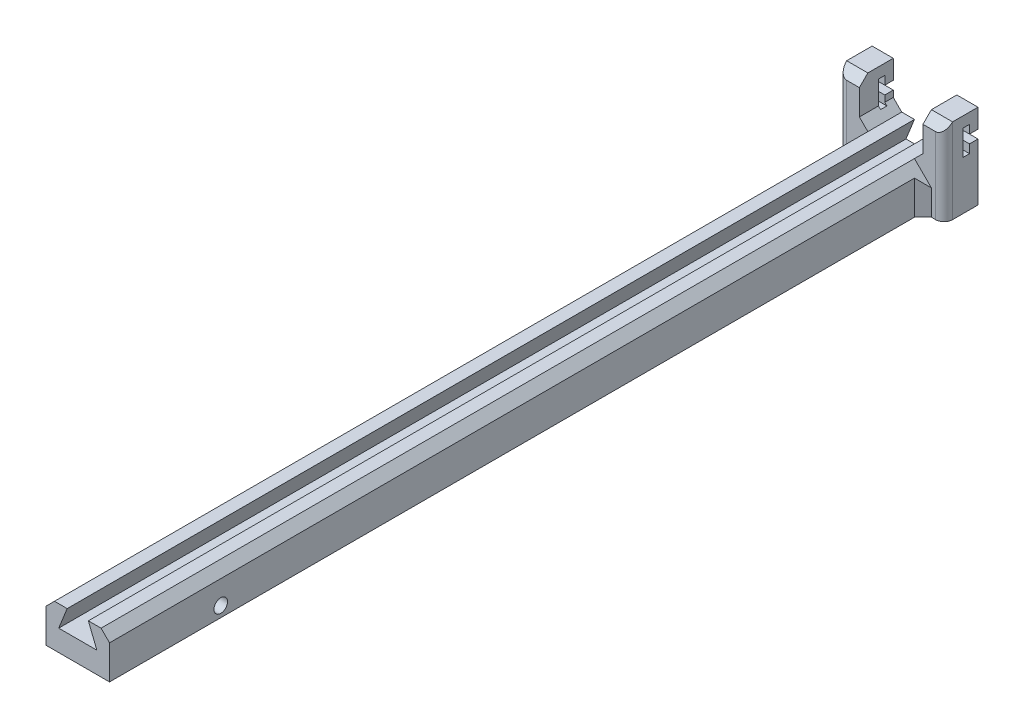
SolidWorks part; units mm, degrees
ref_plane "Front Plane" through (0, 0, 0) normal (0, 0, 1) x (1, 0, 0)
ref_plane "Top Plane" through (0, 0, 0) normal (0, 1, 0) x (1, 0, 0)
ref_plane "Right Plane" through (0, 0, 0) normal (1, 0, 0) x (0, 0, -1)
sketch "Sketch1" plane through (0, 0, 0) normal (0, 1, 0) x (1, 0, 0)
  line L1 (-7.5, -100) -> (7.5, -100)
  line L2 (-7.5, -100) -> (-7.5, 100)
  line L3 (-7.5, 100) -> (7.5, 100)
  line L4 (7.5, -100) -> (7.5, 100)
  line L5 (-7.5, -100) -> (7.5, 100) construction
  line L6 (-7.5, 100) -> (7.5, -100) construction
  point P0 (0, 0)
  dimension "D1" = 200
  dimension "D2" = 15
extrude "Boss-Extrude1" add sketch "Sketch1" along normal blind 10
sketch "Sketch2" plane through (0, 0, 100) normal (0, 0, 1) x (1, 0, 0)
  line L0 (-2.5, 10) -> (-4.5, 5)
  line L1 (-7.5, 10) -> (7.5, 10) construction
  line L2 (-4.5, 5) -> (4.5, 5)
  line L3 (4.5, 5) -> (2.5, 10)
  line L4 (2.5, 10) -> (-2.5, 10)
  line L5 (-7.5, 10) -> (-7.5, 0) construction
  line L6 (7.5, 10) -> (7.5, 0) construction
  line L7 (-7.5, 0) -> (7.5, 0) construction
  dimension "D1" = 5
  dimension "D2" = 5
  dimension "D3" = 5
  dimension "D4" = 3
  dimension "D5" = 3
extrude "Cut-Extrude1" cut sketch "Sketch2" against normal blind 210
sketch "Sketch3" plane through (0, 0, 0) normal (0, -1, 0) x (1, 0, 0)
  line L1 (-7.5, -100) -> (-12.5, -100)
  line L2 (-7.5, -100) -> (-7.5, -92)
  line L3 (-7.5, -92) -> (-12.5, -92)
  line L4 (-12.5, -100) -> (-12.5, -92)
  line L5 (7.5, -100) -> (12.5, -100)
  line L6 (7.5, -100) -> (7.5, -92)
  line L7 (7.5, -92) -> (12.5, -92)
  line L8 (12.5, -100) -> (12.5, -92)
  dimension "D1" = 5
  dimension "D2" = 5
  dimension "D3" = 8
  dimension "D4" = 8
extrude "Boss-Extrude2" add sketch "Sketch3" against normal blind 20
sketch "Sketch4" plane through (12.5, 0, 0) normal (1, 0, 0) x (0, 0, -1)
  line L0 (100, 20) -> (92, 20) construction
  line L1 (96.5, 17.5) -> (98, 17.5)
  line L2 (96.5, 17.5) -> (96.5, 11.5)
  line L3 (96.5, 11.5) -> (98, 11.5)
  line L4 (98, 17.5) -> (98, 15.5)
  line L5 (100, 20) -> (100, 0) construction
  line L6 (98, 13.5) -> (98, 11.5)
  line L7 (98, 15.5) -> (100, 15.5)
  line L9 (98, 13.5) -> (100, 13.5)
  line L10 (100, 15.5) -> (100, 13.5)
  dimension "D1" = 6
  dimension "D2" = 1.5
  dimension "D3" = 2.5
  dimension "D4" = 2
  dimension "D5" = 2
  dimension "D6" = 2
extrude "Cut-Extrude3" cut sketch "Sketch4" against normal blind 40
sketch "Sketch6" plane through (0, 5, 0) normal (0, 1, 0) x (1, 0, 0)
  line L0 (-2.5, -100) -> (-2.5, 100) construction
  line L1 (-2.5, -85) -> (2.5, -85)
  line L2 (-2.5, -85) -> (-2.5, -70)
  line L3 (-2.5, -70) -> (2.5, -70)
  line L4 (2.5, -85) -> (2.5, -70)
  line L5 (2.5, 100) -> (2.5, -100) construction
  line L6 (-4.5, -100) -> (4.5, -100) construction
  dimension "D1" = 15
  dimension "D2" = 15
extrude "Cut-Extrude4" cut sketch "Sketch6" against normal blind 40
sketch "Sketch7" plane through (7.5, 0, 0) normal (1, 0, 0) x (0, 0, -1)
  line L0 (-100, 0) -> (92, 0) construction
  line L1 (-70, 0) -> (-70, 5) construction
  circle A0 centre (-73.75, 2.5) radius 1.6
  dimension "D1" = 3.2
  dimension "D2" = 2.5
  dimension "D3" = 3.75
extrude "Cut-Extrude5" cut sketch "Sketch7" against normal blind 24
chamfer "Chamfer1" distance 2 angle 45 2 edges at (-7.5, 10, -96) (7.5, 10, -96)
chamfer "Chamfer2" distance 2 angle 45 2 edges at (7.5, 10, 4) (-7.5, 10, 4)
chamfer "Chamfer3" distance 2 angle 45 2 edges at (7.5, 4, -92) (-7.5, 4, -92)
chamfer "Chamfer4" distance 2 angle 45 2 edges at (10, 20, -92) (-10, 20, -92)
fillet "Fillet1" radius 2 2 edges at (12.5, 9, -92) (-12.5, 9, -92)
